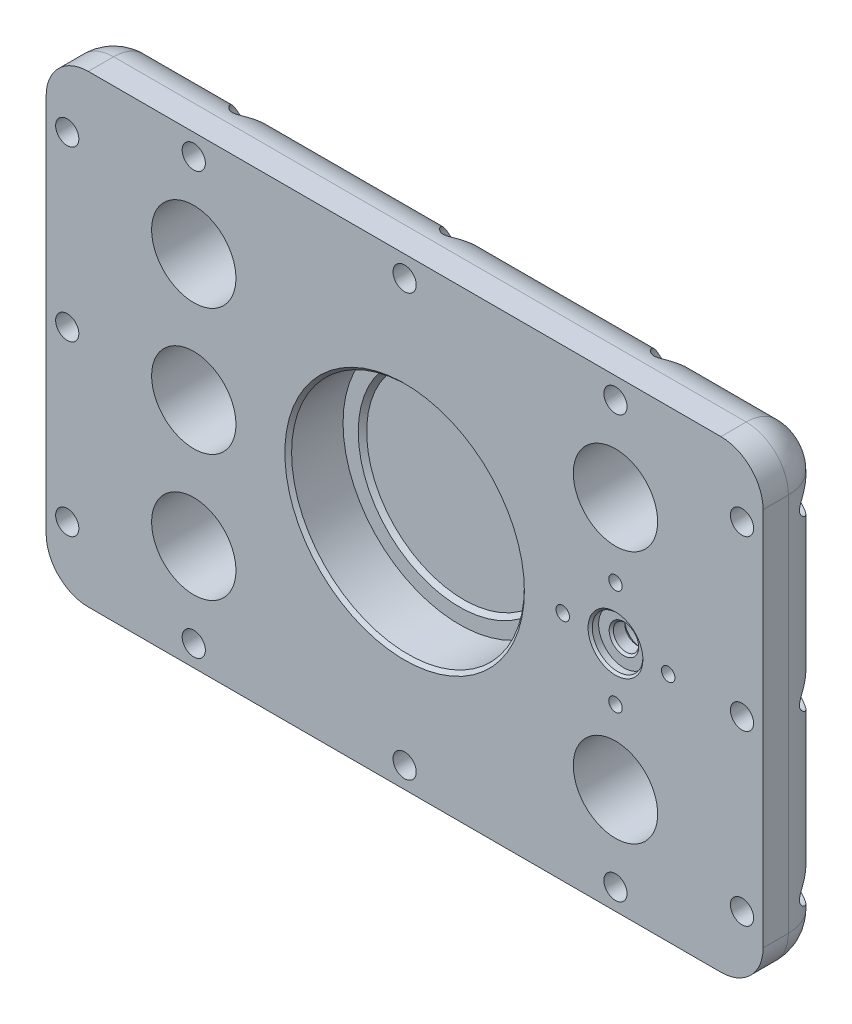
SolidWorks part; units mm, degrees
ref_plane "Front Plane" through (0, 0, 0) normal (0, 0, 1) x (1, 0, 0)
ref_plane "Top Plane" through (0, 0, 0) normal (0, 1, 0) x (1, 0, 0)
ref_plane "Right Plane" through (0, 0, 0) normal (1, 0, 0) x (0, 0, -1)
sketch "Sketch1" plane through (0, 0, 0) normal (0, 0, 1) x (1, 0, 0)
  line L1 (-85, 55) -> (85, 55)
  line L2 (-85, 55) -> (-85, -55)
  line L3 (-85, -55) -> (85, -55)
  line L4 (85, 55) -> (85, -55)
  line L5 (-85, 55) -> (85, -55) construction
  line L6 (-85, -55) -> (85, 55) construction
  point P0 (0, 0)
  dimension "D1" = 170
  dimension "D2" = 110
extrude "Boss-Extrude1" add sketch "Sketch1" along normal blind 16
fillet "Fillet1" radius 10 4 edges at (-85, -55, 8) (85, -55, 8) (85, 55, 8) (-85, 55, 8)
sketch "Sketch2" plane through (0, 0, 16) normal (0, 0, 1) x (1, 0, 0)
  circle A0 centre (0, 0) radius 27.6
  dimension "D1" = 55.2
extrude "Cut-Extrude1" cut sketch "Sketch2" against normal blind 13
sketch "Sketch3" plane through (0, 0, 3) normal (0, 0, 1) x (1, 0, 0)
  circle A0 centre (0, 0) radius 23
  dimension "D1" = 46
extrude "Cut-Extrude2" cut sketch "Sketch3" against normal blind 1
chamfer "Chamfer1" distance 1 angle 45 1 edges at (23, 0, 3)
sketch "Sketch4" plane through (0, 0, 16) normal (0, 0, 1) x (1, 0, 0)
  line L0 (-1000, 0) -> (49000, 0) construction
  circle A0 centre (50, 0) radius 6
  dimension "D1" = 12
  dimension "D2" = 50
extrude "Cut-Extrude4" cut sketch "Sketch4" against normal blind 2
sketch "Sketch5" plane through (0, 0, 14) normal (0, 0, 1) x (1, 0, 0)
  circle A0 centre (50, 0) radius 3
  circle A1 centre (50, 0) radius 6 construction
  point P3 (0, 0)
  point P4 (0, 0)
  dimension "D1" = 6
extrude "Cut-Extrude3" cut sketch "Sketch5" against normal through all
chamfer "Chamfer2" distance 0.8 angle 45 1 edges at (27.6, 0, 16)
chamfer "Chamfer3" distance 0.5 angle 45 2 edges at (53, 0, 14) (56, 0, 16)
sketch "Sketch6" plane through (0, 0, 0) normal (0, 0, -1) x (-1, 0, 0)
  line L0 (-1050, 0) -> (48950, 0) construction
  circle A0 centre (-50, 0) radius 12.5 construction
  circle A1 centre (-62.5, 0) radius 1.6
  circle A2 centre (-50, 12.5) radius 1.6
  circle A3 centre (-50, 0) radius 12.5 construction
  circle A4 centre (-37.5, 0) radius 1.6
  circle A5 centre (-50, 0) radius 12.5 construction
  circle A6 centre (-50, -12.5) radius 1.6
  circle A7 centre (-50, 0) radius 12.5 construction
  point P19 (-50, 0)
  dimension "D1" = 25
  dimension "D2" = 3.2
  dimension "D3" = 4
extrude "Cut-Extrude5" cut sketch "Sketch6" against normal through all
sketch "Sketch7" plane through (0, 0, 0) normal (0, 0, -1) x (-1, 0, 0)
  circle A0 centre (-62.5, 0) radius 3
  dimension "D1" = 6
extrude "Cut-Extrude6" cut sketch "Sketch7" against normal blind 10
pattern_circular "CirPattern1" count 4 over 360 about axis through (50, 0, 0) along (0, 0, 1) of "Cut-Extrude6"
chamfer "Chamfer4" distance 0.5 angle 45 5 edges at (53, 0, 0) (50, -9.5, 0) (40.5, 0, 0) (50, 9.5, 0) (59.5, 0, 0)
sketch "Sketch8" plane through (0, 0, 0) normal (0, 0, -1) x (-1, 0, 0)
  circle A0 centre (-50, 0) radius 8
  dimension "D1" = 16
extrude "Cut-Extrude7" cut sketch "Sketch8" against normal blind 10
chamfer "Chamfer5" distance 0.8 angle 45 2 edges at (42, 0, 0) (47, 0, 10)
fillet "Fillet2" radius 10 8 edges at (82.0711, 52.0711, 0) (85, 0, 0) (82.0711, -52.0711, 0) (0, -55, 0) (-82.0711, -52.0711, 0) (-85, 0, 0) (-82.0711, 52.0711, 0) (0, 55, 0)
sketch "Sketch10" plane through (0, 0, 0) normal (0, 0, -1) x (-1, 0, 0)
  circle A0 centre (-80, 40) radius 2.75
  circle A1 centre (-80, 0) radius 2.75
  circle A2 centre (-80, -40) radius 2.75
  circle A3 centre (-50, -50) radius 2.75
  circle A4 centre (0, -50) radius 2.75
  circle A5 centre (50, -50) radius 2.75
  circle A6 centre (80, -40) radius 2.75
  circle A7 centre (80, 0) radius 2.75
  circle A8 centre (80, 40) radius 2.75
  circle A9 centre (50, 50) radius 2.75
  circle A10 centre (0, 50) radius 2.75
  circle A11 centre (-50, 50) radius 2.75
  dimension "D1" = 5.5
extrude "Cut-Extrude8" cut sketch "Sketch10" against normal through all
sketch "Sketch11" plane through (0, 0, 0) normal (0, 0, -1) x (-1, 0, 0)
  circle A0 centre (-50, 50) radius 4.5
  circle A1 centre (-80, 40) radius 4.5
  circle A2 centre (-80, 0) radius 4.5
  circle A3 centre (-80, -40) radius 4.5
  circle A4 centre (-50, -50) radius 4.5
  circle A5 centre (0, -50) radius 4.5
  circle A6 centre (50, -50) radius 4.5
  circle A7 centre (80, -40) radius 4.5
  circle A8 centre (80, 0) radius 4.5
  circle A9 centre (80, 40) radius 4.5
  circle A10 centre (50, 50) radius 4.5
  circle A11 centre (0, 50) radius 4.5
  dimension "D1" = 9
extrude "Cut-Extrude9" cut sketch "Sketch11" against normal blind 10
sketch "Sketch15" plane through (0, 0, 0) normal (0, 0, -1) x (-1, 0, 0)
  line L0 (-75, 45) -> (-75, -45) construction
  line L1 (75, 45) -> (-75, 45) construction
  circle A5 centre (-50, -30) radius 10
  circle A6 centre (50, -30) radius 10
  circle A7 centre (50, 0) radius 10
  circle A8 centre (50, 30) radius 10
  circle A9 centre (-50, 30) radius 10
  dimension "D1" = 20
  dimension "D2" = 25
  dimension "D3" = 125
  dimension "D4" = 15
  dimension "D5" = 45
  dimension "D6" = 75
extrude "Cut-Extrude10" cut sketch "Sketch15" against normal through all
